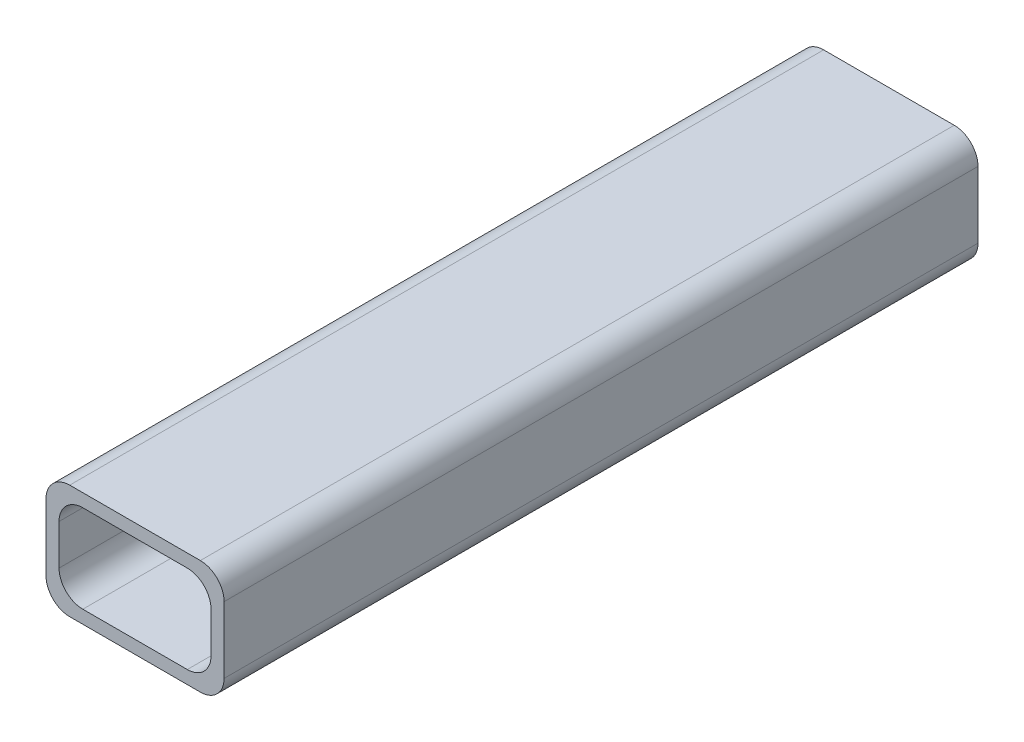
SolidWorks part; units mm, degrees
material "Fibre de verre A"
ref_plane "Plan de face" through (0, 0, 0) normal (0, 0, 1) x (1, 0, 0)
ref_plane "Plan de dessus" through (0, 0, 0) normal (0, 1, 0) x (1, 0, 0)
ref_plane "Plan de droite" through (0, 0, 0) normal (1, 0, 0) x (0, 0, -1)
sketch "Esquisse1" plane through (0, 0, 0) normal (0, 0, 1) x (1, 0, 0)
  line L0 (0, 0) -> (0, 50000) construction
  line L1 (-15, -9.6) -> (15, -9.6)
  line L2 (-15, -9.6) -> (-15, 9.6)
  line L3 (-15, 9.6) -> (15, 9.6)
  line L4 (15, -9.6) -> (15, 9.6)
  line L5 (0, 0) -> (50000, 0) construction
  line L7 (-12.8, -7.4) -> (12.8, -7.4)
  line L8 (-12.8, -7.4) -> (-12.8, 7.4)
  line L9 (-12.8, 7.4) -> (12.8, 7.4)
  line L10 (12.8, -7.4) -> (12.8, 7.4)
  point P0 (0, 0)
  point P6 (0, 0)
  dimension "D1" = 2.2
  dimension "D2" = 2.2
  dimension "D3" = 30
  dimension "D4" = 2.2
  dimension "D5" = 2.2
  dimension "D6" = 19.2
extrude "Boss.-Extru.1" add sketch "Esquisse1" along normal blind 63.5 and the other way blind 63.5
fillet "Congé3" radius 4 8 edges at (-12.8, -7.4, 0) (12.8, -7.4, 0) (12.8, 7.4, 0) (-12.8, 7.4, 0) (-15, -9.6, 0) (15, -9.6, 0) (15, 9.6, 0) (-15, 9.6, 0)
equation "\"longueur\"= 5 * 25.4"
equation "\"D1@Boss.-Extru.1\"=\"longueur\"/2"
equation "\"D2@Boss.-Extru.1\"=\"longueur\"/2"
